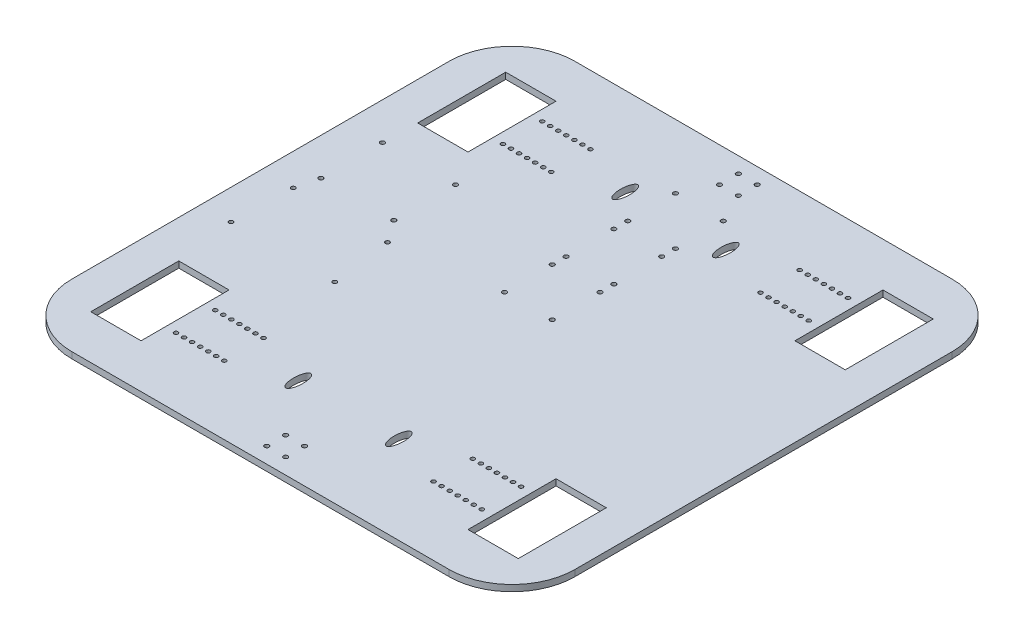
SolidWorks part; units mm, degrees
ref_plane "Front Plane" through (0, 0, 0) normal (0, 0, 1) x (1, 0, 0)
ref_plane "Top Plane" through (0, 0, 0) normal (0, 1, 0) x (1, 0, 0)
ref_plane "Right Plane" through (0, 0, 0) normal (1, 0, 0) x (0, 0, -1)
sketch "Sketch1" plane through (0, 0, 0) normal (0, 1, 0) x (1, 0, 0)
  line L0 (0, -1000) -> (0, 49000) construction
  line L1 (-170, 165) -> (-130, 165)
  line L2 (-170, 165) -> (-170, 95)
  line L3 (-170, 95) -> (-130, 95)
  line L4 (-130, 165) -> (-130, 95)
  line L5 (170, 95) -> (130, 95)
  line L6 (130, 165) -> (130, 95)
  line L7 (170, 165) -> (130, 165)
  line L8 (170, 165) -> (170, 95)
  line L9 (-1000, 0) -> (49000, 0) construction
  line L10 (-10, 190) -> (10, 190)
  line L11 (-10, 190) -> (-10, 170)
  line L12 (-10, 170) -> (10, 170)
  line L13 (10, 190) -> (10, 170)
  line L14 (-1010, 180) -> (48990, 180) construction
  line L15 (-1010, -180) -> (48990, -180) construction
  line L16 (0, 1000) -> (0, -49000) construction
  line L17 (-10, -170) -> (10, -170)
  line L18 (10, -190) -> (10, -170)
  line L19 (-10, -190) -> (10, -190)
  line L20 (-10, -190) -> (-10, -170)
  line L21 (170, -165) -> (170, -95)
  line L22 (-200, 200) -> (200, 200)
  line L23 (-200, 200) -> (-200, -200)
  line L24 (-200, -200) -> (200, -200)
  line L25 (200, 200) -> (200, -200)
  line L26 (170, -165) -> (130, -165)
  line L27 (130, -165) -> (130, -95)
  line L28 (170, -95) -> (130, -95)
  line L29 (-170, -95) -> (-130, -95)
  line L30 (-130, -165) -> (-130, -95)
  line L31 (-170, -165) -> (-130, -165)
  line L32 (-170, -165) -> (-170, -95)
  circle A0 centre (0, 0) radius 200 construction
  circle A1 centre (-7.5, 187.5) radius 1.75
  circle A2 centre (7.5, 187.5) radius 1.75
  circle A3 centre (7.5, 172.5) radius 1.75
  circle A4 centre (-7.5, 172.5) radius 1.75
  circle A5 centre (7.5, -187.5) radius 1.75
  circle A6 centre (-7.5, -187.5) radius 1.75
  circle A7 centre (-7.5, -172.5) radius 1.75
  circle A8 centre (7.5, -172.5) radius 1.75
  point P8 (-150, 165)
  point P19 (0, 190)
  point P22 (-10, 180)
  dimension "D1" = 400
  dimension "D7" = 3.5
  dimension "D2" = 40
  dimension "D3" = 70
  dimension "D4" = 150
  dimension "D5" = 20
  dimension "D6" = 180
  dimension "D8" = 2.5
  dimension "D9" = 2.5
  dimension "D10" = 35
extrude "Boss-Extrude2" add sketch "Sketch1" along normal blind 5 contours L25 L22 L23 L24 L1 L4 L3 L2 L7 L8 L5 L6 L10 L13 L12 L11 L19 L20 L17 L18 | L20 L19 L18 L17 A6 A5 A7 A8 | L13 L10 L11 L12 A2 A1 A3 A4 region at (0, 0, -180) region at (0, 0, 180) region at (0, 0, 0)
fillet "Fillet1" radius 50 4 edges at (200, 2.5, -200) (200, 2.5, 200) (-200, 2.5, 200) (-200, 2.5, -200)
sketch "Sketch2" plane through (0, 5, 0) normal (0, 1, 0) x (1, 0, 0)
  line L0 (-1094.0419, 130) -> (48905.9581, 130) construction
  line L1 (-130, 148.8) -> (-78.5, 148.8) construction
  line L2 (-130, 148.8) -> (-130, 111.2) construction
  line L3 (-130, 111.2) -> (-78.5, 111.2) construction
  line L4 (-78.5, 148.8) -> (-78.5, 111.2) construction
  line L5 (-130, 165) -> (-130, 95) construction
  line L6 (-170, 165) -> (-170, 95) construction
  line L7 (0, -1000) -> (0, 49000) construction
  line L8 (130, 111.2) -> (78.5, 111.2) construction
  line L9 (78.5, 148.8) -> (78.5, 111.2) construction
  line L10 (130, 148.8) -> (78.5, 148.8) construction
  line L11 (130, 148.8) -> (130, 111.2) construction
  line L12 (-1000, 0) -> (49000, 0) construction
  line L13 (130, -148.8) -> (130, -111.2) construction
  line L14 (130, -148.8) -> (78.5, -148.8) construction
  line L15 (78.5, -148.8) -> (78.5, -111.2) construction
  line L16 (130, -111.2) -> (78.5, -111.2) construction
  line L17 (-78.5, -148.8) -> (-78.5, -111.2) construction
  line L18 (-130, -111.2) -> (-78.5, -111.2) construction
  line L19 (-130, -148.8) -> (-130, -111.2) construction
  line L20 (-130, -148.8) -> (-78.5, -148.8) construction
  line L21 (-1094.0419, -130) -> (48905.9581, -130) construction
  circle A0 centre (-121.6, 145.6) radius 1.6
  circle A1 centre (-115.2, 145.6) radius 1.6
  circle A2 centre (-108.8, 145.6) radius 1.6
  circle A3 centre (-102.4, 145.6) radius 1.6
  circle A4 centre (-96, 145.6) radius 1.6
  circle A5 centre (-89.6, 145.6) radius 1.6
  circle A6 centre (-83.2, 145.6) radius 1.6
  circle A7 centre (-83.2, 114.4) radius 1.6
  circle A8 centre (-89.6, 114.4) radius 1.6
  circle A9 centre (-96, 114.4) radius 1.6
  circle A10 centre (-102.4, 114.4) radius 1.6
  circle A11 centre (-108.8, 114.4) radius 1.6
  circle A12 centre (-115.2, 114.4) radius 1.6
  circle A13 centre (-121.6, 114.4) radius 1.6
  circle A14 centre (83.2, 114.4) radius 1.6
  circle A15 centre (89.6, 114.4) radius 1.6
  circle A16 centre (96, 114.4) radius 1.6
  circle A17 centre (102.4, 114.4) radius 1.6
  circle A18 centre (108.8, 114.4) radius 1.6
  circle A19 centre (115.2, 114.4) radius 1.6
  circle A20 centre (121.6, 114.4) radius 1.6
  circle A21 centre (83.2, 145.6) radius 1.6
  circle A22 centre (89.6, 145.6) radius 1.6
  circle A23 centre (96, 145.6) radius 1.6
  circle A24 centre (102.4, 145.6) radius 1.6
  circle A25 centre (108.8, 145.6) radius 1.6
  circle A26 centre (115.2, 145.6) radius 1.6
  circle A27 centre (121.6, 145.6) radius 1.6
  circle A28 centre (121.6, -145.6) radius 1.6
  circle A29 centre (115.2, -145.6) radius 1.6
  circle A30 centre (108.8, -145.6) radius 1.6
  circle A31 centre (102.4, -145.6) radius 1.6
  circle A32 centre (96, -145.6) radius 1.6
  circle A33 centre (89.6, -145.6) radius 1.6
  circle A34 centre (83.2, -145.6) radius 1.6
  circle A35 centre (121.6, -114.4) radius 1.6
  circle A36 centre (115.2, -114.4) radius 1.6
  circle A37 centre (108.8, -114.4) radius 1.6
  circle A38 centre (102.4, -114.4) radius 1.6
  circle A39 centre (96, -114.4) radius 1.6
  circle A40 centre (89.6, -114.4) radius 1.6
  circle A41 centre (83.2, -114.4) radius 1.6
  circle A42 centre (-121.6, -114.4) radius 1.6
  circle A43 centre (-115.2, -114.4) radius 1.6
  circle A44 centre (-108.8, -114.4) radius 1.6
  circle A45 centre (-102.4, -114.4) radius 1.6
  circle A46 centre (-96, -114.4) radius 1.6
  circle A47 centre (-89.6, -114.4) radius 1.6
  circle A48 centre (-83.2, -114.4) radius 1.6
  circle A49 centre (-83.2, -145.6) radius 1.6
  circle A50 centre (-89.6, -145.6) radius 1.6
  circle A51 centre (-96, -145.6) radius 1.6
  circle A52 centre (-102.4, -145.6) radius 1.6
  circle A53 centre (-108.8, -145.6) radius 1.6
  circle A54 centre (-115.2, -145.6) radius 1.6
  circle A55 centre (-121.6, -145.6) radius 1.6
  point P9 (-130, 130)
  point P40 (-170, 130)
  dimension "D3" = 3.2
  dimension "D7" = 6.4
  dimension "D5" = 8.4
  dimension "D1" = 37.6
  dimension "D2" = 4.7
  dimension "D4" = 31.2
  dimension "D6" = 7
extrude "Cut-Extrude1" cut sketch "Sketch2" against normal blind 5
sketch "Sketch3" plane through (0, 5, 0) normal (0, 1, 0) x (1, 0, 0)
  line L0 (-150, -200) -> (150, -200) construction
  line L1 (-190, 3.34) -> (-88.4, 3.34) construction
  line L2 (-190, 3.34) -> (-190, -50) construction
  line L3 (-190, -50) -> (-88.4, -50) construction
  line L4 (-88.4, 3.34) -> (-88.4, -50) construction
  line L5 (-200, 150) -> (-200, -150) construction
  circle A0 centre (-176.03, -47.46) radius 1.65
  circle A1 centre (-174.76, 0.8) radius 1.65
  circle A2 centre (-93.48, -47.46) radius 1.65
  circle A3 centre (-99.83, 0.8) radius 1.65
  dimension "D5" = 3.3
  dimension "D8" = 3.3
  dimension "D9" = 96.52
  dimension "D10" = 90.17
  dimension "D1" = 101.6
  dimension "D2" = 53.34
  dimension "D3" = 13.97
  dimension "D4" = 2.54
  dimension "D6" = 15.24
  dimension "D7" = 50.8
  dimension "D11" = 150
  dimension "D12" = 10
extrude "Cut-Extrude2" cut sketch "Sketch3" against normal blind 10 contours A1 | A2 | L2 L1 L4 L3 | A0 | A3 region at (-174.76, 5, -0.8) region at (-93.48, 5, 47.46)
sketch "Sketch4" plane through (0, 5, 0) normal (0, 1, 0) x (1, 0, 0)
  line L0 (-19, 149) -> (19, 149) construction
  line L1 (-1149.7342, 130) -> (48850.2658, 130) construction
  line L2 (-22, 152) -> (22, 152) construction
  line L3 (-22, 152) -> (-22, 108) construction
  line L4 (-22, 108) -> (22, 108) construction
  line L5 (22, 152) -> (22, 108) construction
  line L6 (-19, 111) -> (19, 111) construction
  line L7 (-19, 100) -> (19, 100) construction
  line L8 (-1231.3219, 81) -> (48768.6781, 81) construction
  line L9 (-22, 103) -> (22, 103) construction
  line L10 (-22, 103) -> (-22, 59) construction
  line L11 (-22, 59) -> (22, 59) construction
  line L12 (22, 103) -> (22, 59) construction
  line L13 (-19, 62) -> (19, 62) construction
  line L14 (-19, 13) -> (19, 13) construction
  line L15 (-22, 10) -> (22, 10) construction
  line L16 (-130, 165) -> (-130, 95) construction
  line L17 (-150, 200) -> (150, 200) construction
  line L18 (22, 54) -> (22, 10) construction
  line L19 (-22, 54) -> (-22, 10) construction
  line L20 (-19, 51) -> (19, 51) construction
  line L21 (-22, 54) -> (22, 54) construction
  circle A0 centre (-19, 149) radius 1.75
  circle A1 centre (19, 149) radius 1.75
  circle A2 centre (19, 111) radius 1.75
  circle A3 centre (-19, 111) radius 1.75
  circle A4 centre (-19, 100) radius 1.75
  circle A5 centre (19, 100) radius 1.75
  circle A6 centre (19, 62) radius 1.75
  circle A7 centre (-19, 62) radius 1.75
  circle A8 centre (-19, 13) radius 1.75
  circle A9 centre (19, 13) radius 1.75
  circle A10 centre (-19, 51) radius 1.75
  circle A11 centre (19, 51) radius 1.75
  point P9 (0, 149)
  point P10 (0, 152)
  point P14 (-22, 130)
  point P26 (0, 100)
  point P27 (0, 103)
  point P31 (-22, 81)
  point P38 (-130, 130)
  point P39 (0, 200)
  point P40 (0, 108)
  dimension "D1" = 3.5
  dimension "D5" = 3.5
  dimension "D2" = 38
  dimension "D3" = 44
  dimension "D4" = 38
  dimension "D6" = 38
  dimension "D7" = 44
  dimension "D8" = 38
  dimension "D9" = 5
  dimension "D11" = 5
  dimension "D10" = 2
extrude "Cut-Extrude3" cut sketch "Sketch4" against normal blind 10
sketch "Sketch5" plane through (0, 5, 0) normal (0, 1, 0) x (1, 0, 0)
  line L0 (-1136.3236, 43) -> (48863.6764, 43) construction
  line L1 (-174, 15) -> (-89, 15) construction
  line L2 (-174, 15) -> (-174, 71) construction
  line L3 (-174, 71) -> (-89, 71) construction
  line L4 (-89, 15) -> (-89, 71) construction
  line L5 (-180, 10) -> (-83, 10) construction
  line L6 (-180, 10) -> (-180, 76) construction
  line L7 (-180, 76) -> (-83, 76) construction
  line L8 (-83, 10) -> (-83, 76) construction
  line L9 (-200, 150) -> (-200, -150) construction
  line L10 (-150, -200) -> (150, -200) construction
  circle A0 centre (-170.5, 67.5) radius 1.75
  circle A1 centre (-112.5, 67.5) radius 1.75
  circle A2 centre (-112.5, 18.5) radius 1.75
  circle A3 centre (-170.5, 18.5) radius 1.75
  dimension "D4" = 3.5
  dimension "D5" = 3.5
  dimension "D1" = 56
  dimension "D2" = 85
  dimension "D3" = 58
  dimension "D6" = 3.5
  dimension "D7" = 49
  dimension "D8" = 3.5
  dimension "D9" = 5
  dimension "D10" = 5
  dimension "D11" = 6
  dimension "D12" = 6
  dimension "D13" = 20
  dimension "D14" = 210
extrude "Cut-Extrude4" cut sketch "Sketch5" against normal blind 10
sketch "Sketch6" plane through (0, 5, 0) normal (0, 1, 0) x (1, 0, 0)
  line L0 (-130, 165) -> (-130, 95) construction
  line L1 (0, -800) -> (0, 49200) construction
  line L2 (-150, 200) -> (150, 200) construction
  line L3 (-1200, 0) -> (48800, 0) construction
  line L4 (-200, 150) -> (-200, -150) construction
  ellipse E0 centre (-40, 130) end of major axis (-40, 140) minor radius 3.75
  ellipse E1 centre (40, 130) end of major axis (40, 140) minor radius 3.75
  ellipse E2 centre (40, -130) end of major axis (40, -140) minor radius 3.75
  ellipse E3 centre (-40, -130) end of major axis (-40, -140) minor radius 3.75
  point P13 (-130, 130)
  point P14 (-200, 0)
  point P26 (0, 200)
  dimension "D1" = 90
  dimension "D2" = 20
  dimension "D3" = 7.5
extrude "Cut-Extrude5" cut sketch "Sketch6" against normal blind 10
